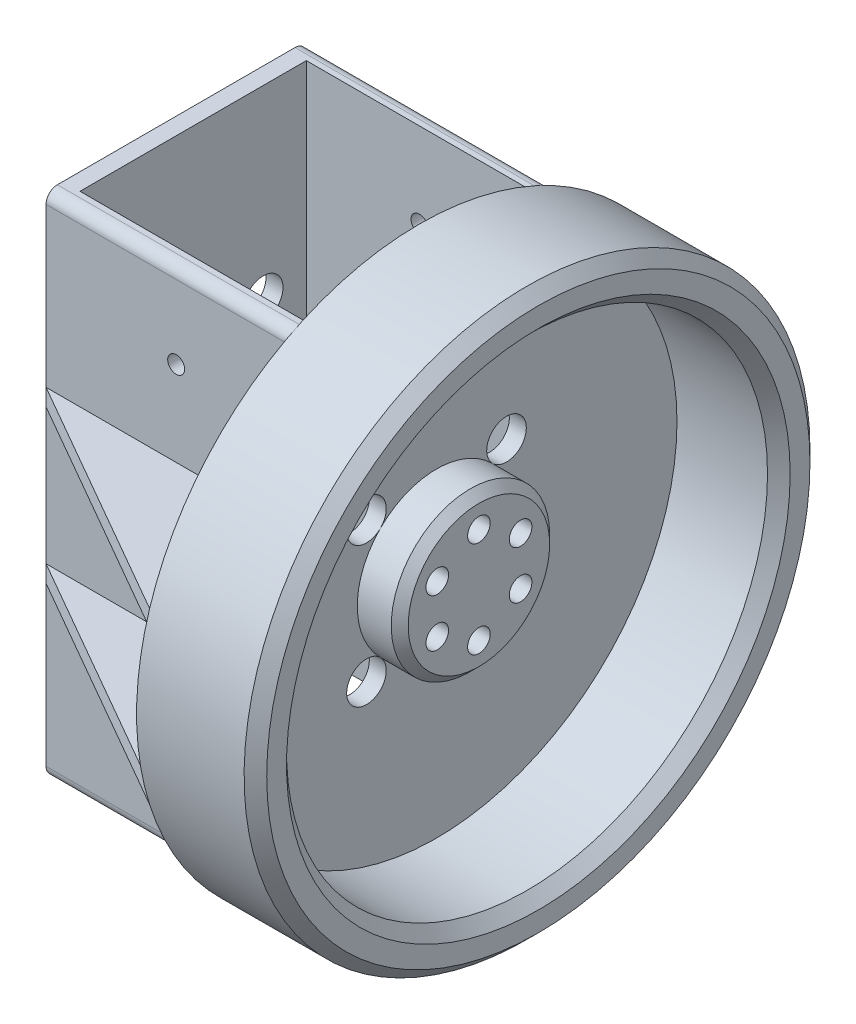
SolidWorks part; units mm, degrees
material "PA Type 6"
ref_plane "Front Plane" through (0, 0, 0) normal (0, 0, 1) x (1, 0, 0)
ref_plane "Top Plane" through (0, 0, 0) normal (0, 1, 0) x (1, 0, 0)
ref_plane "Right Plane" through (0, 0, 0) normal (1, 0, 0) x (0, 0, -1)
sketch "Esquisse3" plane through (0, 0, 0) normal (1, 0, 0) x (0, 0, -1)
  circle A0 centre (0, 0) radius 42.5
  circle A1 centre (0, 0) radius 50
  dimension "D1" = 85
  dimension "D2" = 100
extrude "Boss.-Extru.2" add sketch "Esquisse3" along normal blind 18
sketch "Esquisse4" plane through (0, 0, 0) normal (-1, 0, 0) x (0, 0, 1)
  circle A0 centre (0, 0) radius 50
  circle A1 centre (0, 0) radius 50 construction
extrude "Boss.-Extru.3" add sketch "Esquisse4" along normal blind 3
sketch "Esquisse5" plane through (0, 0, 0) normal (1, 0, 0) x (0, 0, -1)
  circle A0 centre (0, 0) radius 14
  dimension "D1" = 28
extrude "Boss.-Extru.4" add sketch "Esquisse5" along normal blind 7.5
sketch "Esquisse10" plane through (0, 0, 0) normal (0, 1, 0) x (1, 0, 0)
  line L0 (-3, 50) -> (-3, -50) construction
  line L1 (-46, 23) -> (-3, 23)
  line L2 (-46, 23) -> (-46, -23)
  line L3 (-46, -23) -> (-3, -23)
  line L5 (-43, 20) -> (-3, 20)
  line L6 (-43, 20) -> (-43, -20)
  line L7 (-43, -20) -> (-3, -20)
  line L9 (-3, -23) -> (-3, -20)
  line L10 (-3, 23) -> (-3, 20)
  dimension "D1" = 46
  dimension "D2" = 40
  dimension "D3" = 3
  dimension "D4" = 3
  dimension "D5" = 20
extrude "Boss.-Extru.5" add sketch "Esquisse10" along normal blind 45 and the other way blind 45
fillet "Congé1" radius 2 4 edges at (-24.5, 45, -23) (-24.5, 45, 23) (-24.5, -45, 23) (-24.5, -45, -23)
sketch "Esquisse6" plane through (0, 0, 0) normal (1, 0, 0) x (0, 0, -1)
  line L0 (-12.3744, 12.3744) -> (12.3744, -12.3744) construction
  line L1 (-12.3744, 12.3744) -> (12.3744, 12.3744) construction
  line L2 (-12.3744, 12.3744) -> (-12.3744, -12.3744) construction
  line L3 (-12.3744, -12.3744) -> (12.3744, -12.3744) construction
  line L4 (12.3744, 12.3744) -> (12.3744, -12.3744) construction
  circle A0 centre (-12.3744, 12.3744) radius 3.5
  circle A1 centre (12.3744, 12.3744) radius 3.5
  circle A2 centre (12.3744, -12.3744) radius 3.5
  circle A3 centre (-12.3744, -12.3744) radius 3.5
  dimension "D2" = 7
  dimension "D1" = 35
extrude "Enlèv. mat.-Extru.1" cut sketch "Esquisse6" against normal through all
sketch "Esquisse7" plane through (7.5, 0, 0) normal (1, 0, 0) x (0, 0, -1)
  line L1 (7.3612, -4.25) -> (7.3612, 4.25) construction
  line L2 (7.3612, 4.25) -> (0, 8.5) construction
  line L3 (0, 8.5) -> (-7.3612, 4.25) construction
  line L4 (-7.3612, 4.25) -> (-7.3612, -4.25) construction
  line L5 (-7.3612, -4.25) -> (0, -8.5) construction
  line L6 (0, -8.5) -> (7.3612, -4.25) construction
  circle A0 centre (0, 0) radius 7.3612 construction
  circle A1 centre (0, 8.5) radius 2
  circle A2 centre (7.3612, 4.25) radius 2
  circle A3 centre (7.3612, -4.25) radius 2
  circle A4 centre (0, -8.5) radius 2
  circle A5 centre (-7.3612, -4.25) radius 2
  circle A6 centre (-7.3612, 4.25) radius 2
  dimension "D2" = 4
  dimension "D1" = 17
extrude "Enlèv. mat.-Extru.2" cut sketch "Esquisse7" against normal through all
sketch "Esquisse8" plane through (-3, 0, 0) normal (-1, 0, 0) x (0, 0, 1)
  circle A0 centre (0, -8.5) radius 3.5
  circle A1 centre (7.3612, -4.25) radius 3.5
  circle A2 centre (0, 8.5) radius 3.5
  circle A3 centre (7.3612, 4.25) radius 3.5
  circle A4 centre (-7.3612, -4.25) radius 3.5
  circle A5 centre (-7.3612, 4.25) radius 3.5
  circle A6 centre (-7.3612, -4.25) radius 2 construction
  circle A7 centre (0, -8.5) radius 2 construction
  circle A8 centre (7.3612, -4.25) radius 2 construction
  circle A9 centre (7.3612, 4.25) radius 2 construction
  circle A10 centre (0, 8.5) radius 2 construction
  circle A11 centre (-7.3612, 4.25) radius 2 construction
  dimension "D1" = 7
extrude "Enlèv. mat.-Extru.3" cut sketch "Esquisse8" against normal blind 4 and the other way through all
sketch "Esquisse11" plane through (-3, 0, 0) normal (-1, 0, 0) x (0, 0, 1)
  line L0 (23, -43) -> (23, 43) construction
  line L1 (23, 15) -> (47.697, 15)
  line L2 (23, 15) -> (23, 12)
  line L3 (23, 12) -> (47.697, 12)
  line L4 (47.697, 15) -> (47.697, 12)
  line L5 (-23, -43) -> (-23, 43) construction
  line L6 (23, -12) -> (47.697, -12)
  line L7 (23, -12) -> (23, -15)
  line L8 (23, -15) -> (47.697, -15)
  line L9 (47.697, -12) -> (47.697, -15)
  line L10 (-47.697, -12) -> (-23, -12)
  line L11 (-47.697, -12) -> (-47.697, -15)
  line L12 (-47.697, -15) -> (-23, -15)
  line L13 (-23, -12) -> (-23, -15)
  line L14 (-23, 43) -> (-23, -43) construction
  line L15 (-47.697, 15) -> (-23, 15)
  line L16 (-47.697, 15) -> (-47.697, 12)
  line L17 (-47.697, 12) -> (-23, 12)
  line L18 (-23, 15) -> (-23, 12)
  circle A0 centre (0, 0) radius 50 construction
  dimension "D1" = 3
  dimension "D2" = 12
  dimension "D3" = 12
  dimension "D4" = 0
  dimension "D5" = 0
extrude "Boss.-Extru.6" add sketch "Esquisse11" along normal blind 43
sketch "Esquisse12" plane through (0, -15, 0) normal (0, -1, 0) x (1, 0, 0)
  line L0 (-46, -23) -> (-3, -47.697)
  line L1 (-3, -47.697) -> (-46, -47.697)
  line L2 (-46, -47.697) -> (-46, -23)
  line L3 (-46, 23) -> (-3, 47.697)
  line L4 (-3, 47.697) -> (-46, 47.697)
  line L5 (-46, 47.697) -> (-46, 23)
extrude "Enlèv. mat.-Extru.4" cut sketch "Esquisse12" against normal blind 43
sketch "Esquisse13" plane through (0, 0, -23) normal (0, 0, -1) x (-1, 0, 0)
  line L0 (23, 30) -> (23, -30) construction
  circle A0 centre (23, 30) radius 1.5
  circle A1 centre (23, -30) radius 1.5
  circle A2 centre (23, 0) radius 1.5
  point P6 (27.3319, 0)
  dimension "D3" = 3
  dimension "D1" = 0
  dimension "D2" = 60
  dimension "D4" = 20
extrude "Enlèv. mat.-Extru.5" cut sketch "Esquisse13" against normal through all
chamfer "Chanfrein1" distance 2 angle 45 2 edges at (18, 0, -50) (18, 0, -42.5)
chamfer "Chanfrein2" distance 1.5 angle 45 1 edges at (7.5, 0, -14)
